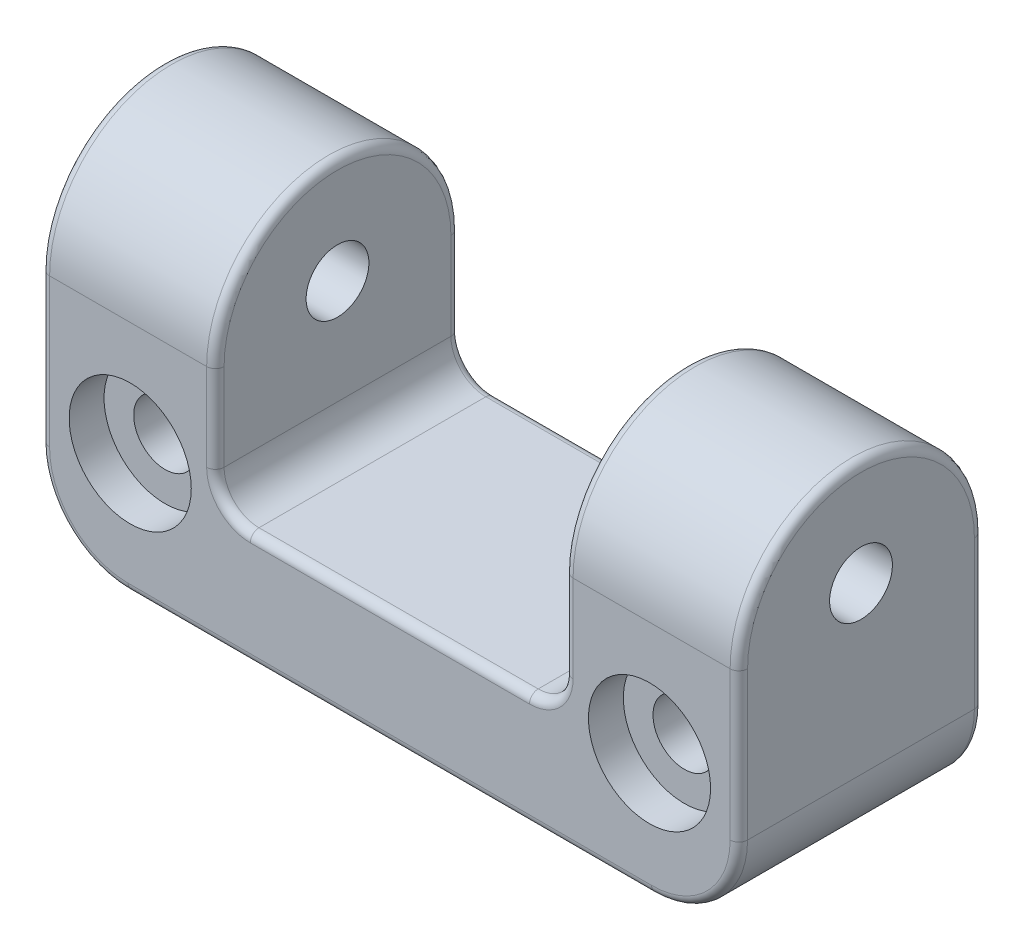
SolidWorks part; units mm, degrees
ref_plane "Front Plane" through (0, 0, 0) normal (0, 0, 1) x (1, 0, 0)
ref_plane "Top Plane" through (0, 0, 0) normal (0, 1, 0) x (1, 0, 0)
ref_plane "Right Plane" through (0, 0, 0) normal (1, 0, 0) x (0, 0, -1)
sketch "Sketch1" plane through (0, 0, 0) normal (0, 0, 1) x (1, 0, 0)
  line L0 (0, 4.1275) -> (0, -4.1275) construction
  line L1 (12.7, -4.1275) -> (-12.7, -4.1275)
  line L2 (12.7, -4.1275) -> (12.7, 4.1275)
  line L3 (12.7, 4.1275) -> (-12.7, 4.1275)
  line L4 (-12.7, -4.1275) -> (-12.7, 4.1275)
  line L5 (12.7, -4.1275) -> (-12.7, 4.1275) construction
  line L6 (12.7, 4.1275) -> (-12.7, -4.1275) construction
  line L7 (25.4, -4.1275) -> (25.4, 22.5425)
  line L8 (-12.7, -4.1275) -> (-25.4, -4.1275)
  line L9 (-12.7, -4.1275) -> (-12.7, 22.5425)
  line L10 (-12.7, 22.5425) -> (-25.4, 22.5425)
  line L11 (-25.4, -4.1275) -> (-25.4, 22.5425)
  line L12 (12.7, -4.1275) -> (25.4, -4.1275)
  line L13 (12.7, -4.1275) -> (12.7, 22.5425)
  line L14 (12.7, 22.5425) -> (25.4, 22.5425)
  circle A0 centre (-18.8976, 4.7625) radius 2.286
  circle A2 centre (18.8976, 4.7625) radius 2.286
  point P0 (0, 0)
  dimension "D1" = 4.572
  dimension "D2" = 25.4
  dimension "D3" = 8.255
  dimension "D4" = 12.7
  dimension "D5" = 26.67
  dimension "D6" = 37.7952
  dimension "D7" = 8.89
extrude "Boss-Extrude1" add sketch "Sketch1" along normal blind 17.78 contours L11 L8 L4 L9 L10 | L4 L1 L2 L3 A0 A2 | L14 L13 L2 L12 L7 region at (0, 0, 0) region at (19.0578, 9.4339, 0) region at (-19.0578, 9.4339, 0)
sketch "Sketch2" plane through (25.4, 0, 0) normal (1, 0, 0) x (0, 0, -1)
  line L0 (-17.78, 22.5425) -> (0, 22.5425) construction
  circle A0 centre (-8.89, 14.2875) radius 2.286
  point P2 (-8.89, 22.5425)
  dimension "D1" = 4.572
  dimension "D2" = 8.255
extrude "Cut-Extrude1" cut sketch "Sketch2" against normal through all
fillet "Fillet1" radius 9.525 4 edges at (19.05, 22.5425, 0) (-19.05, 22.5425, 0) (-19.05, 22.5425, 17.78) (19.05, 22.5425, 17.78)
fillet "Fillet2" radius 6.35 2 edges at (25.4, -4.1275, 8.89) (-25.4, -4.1275, 8.89)
sketch "Sketch3" plane through (0, 0, 17.78) normal (0, 0, 1) x (1, 0, 0)
  circle A0 centre (-18.8976, 4.7625) radius 4.445
  circle A1 centre (18.8976, 4.7625) radius 4.445
  dimension "D1" = 8.89
extrude "Cut-Extrude2" cut sketch "Sketch3" against normal blind 2.54
fillet "Fillet3" radius 2.54 2 edges at (12.7, 4.1275, 8.89) (-12.7, 4.1275, 8.89)
fillet "Fillet4" radius 8.89 2 edges at (19.05, 22.5213, 8.89) (-19.05, 22.5213, 8.89)
fillet "Fillet5" radius 0.635 24 edges at (-25.4, 7.62, 17.78) (-23.5401, -2.2676, 17.78) (0, -4.1275, 17.78) (23.5401, -2.2676, 17.78) (25.4, 7.62, 17.78) (25.4, 21.9075, 8.89) (25.4, 7.62, 0) (23.5401, -2.2676, 0) (0, -4.1275, 0) (-23.5401, -2.2676, 0) (-25.4, 7.62, 0) (-12.7, 9.8425, 0) (-11.9561, 4.8714, 0) (0, 4.1275, 0) (11.9561, 4.8714, 0) (12.7, 9.8425, 0) (12.7, 21.9075, 8.89) (12.7, 9.8425, 17.78) (11.9561, 4.8714, 17.78) (0, 4.1275, 17.78) (-11.9561, 4.8714, 17.78) (-12.7, 9.8425, 17.78) (-25.4, 21.9075, 8.89) (-12.7, 21.9075, 8.89)
